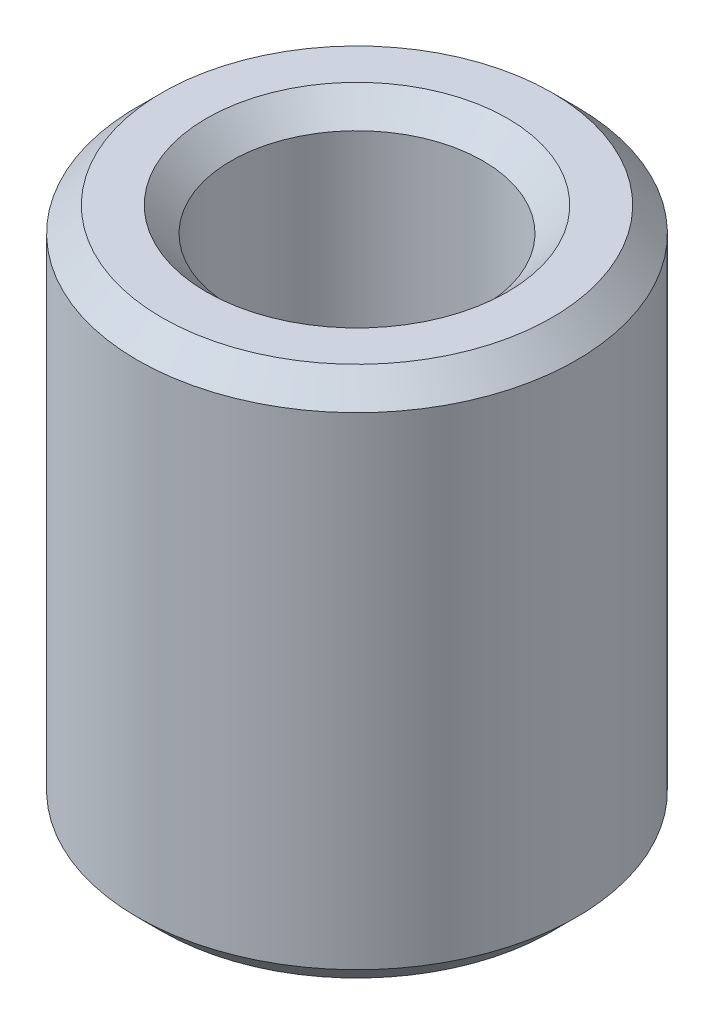
SolidWorks part; units mm, degrees
ref_plane "Front Plane" through (0, 0, 0) normal (0, 0, 1) x (1, 0, 0)
ref_plane "Top Plane" through (0, 0, 0) normal (0, 1, 0) x (1, 0, 0)
ref_plane "Right Plane" through (0, 0, 0) normal (1, 0, 0) x (0, 0, -1)
sketch "Sketch1" plane through (0, 0, 0) normal (0, 1, 0) x (1, 0, 0)
  circle A0 centre (0, 0) radius 20
  dimension "SLEEVE_OD" = 40
extrude "Boss-Extrude1" add sketch "Sketch1" along normal blind 48.4298
sketch "Sketch2" plane through (0, 0, 0) normal (0, 1, 0) x (1, 0, 0)
  circle A0 centre (0, 0) radius 11.4713
  dimension "BORE_D" = 22.9427
extrude "Cut-Extrude1" cut sketch "Sketch2" along normal through all
chamfer "Chamfer1" distance 2.2374 angle 45 4 edges at (0, 48.4298, 11.4713) (0, 0, 11.4713) (0, 0, 20) (0, 48.4298, 20)
